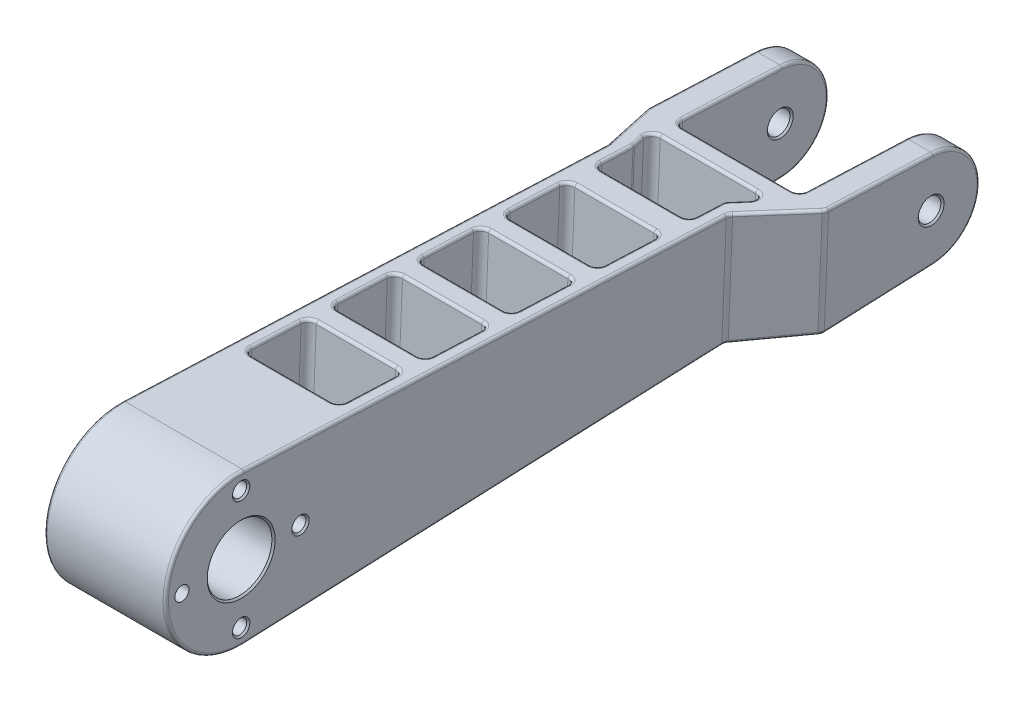
SolidWorks part; units mm, degrees
ref_plane "前视基准面" through (0, 0, 0) normal (0, 0, 1) x (1, 0, 0)
ref_plane "上视基准面" through (0, 0, 0) normal (0, 1, 0) x (1, 0, 0)
ref_plane "右视基准面" through (0, 0, 0) normal (1, 0, 0) x (0, 0, -1)
sketch "草图1" plane through (0, 0, 0) normal (1, 0, 0) x (0, 0, -1)
  line L0 (0.5833, 13.9878) -> (120.375, 8.9922)
  line L1 (0, -14.0122) -> (120.375, -8.9922)
  arc A0 (0.5833, 13.9878) -> (0.5833, -13.9878) centre (0, 0) ccw
  arc A1 (120.375, -8.9922) -> (120.375, 8.9922) centre (120, 0) ccw
  dimension "D1" = 28
  dimension "D2" = 18
  dimension "D3" = 120
extrude "凸台-拉伸1" add sketch "草图1" along normal blind 33 contours L1 A1 L0 A0
sketch "草图2" plane through (0, 0, 0) normal (-1, 0, 0) x (0, 0, 1)
  line L0 (11, 0) -> (0, 0) construction
  line L3 (-120.375, -8.9922) -> (-0.5833, -13.9878)
  line L4 (-0.5833, 13.9878) -> (-120.375, 8.9922)
  line L5 (-120.375, -8.9922) -> (-0.5833, -13.9878)
  line L6 (-0.5833, 13.9878) -> (-120.375, 8.9922)
  circle A0 centre (0, 0) radius 6
  circle A2 centre (11, 0) radius 1.3108
  circle A3 centre (0, -11) radius 1.3108
  circle A4 centre (-11, 0) radius 1.3108
  circle A5 centre (0, 11) radius 1.3108
  circle A9 centre (-120, 0) radius 2.1
  arc A12 (-0.5833, -13.9878) -> (-0.5833, 13.9878) centre (0, 0) ccw
  arc A13 (-120.375, 8.9922) -> (-120.375, -8.9922) centre (-120, 0) ccw
  arc A14 (-0.5833, -13.9878) -> (-0.5833, 13.9878) centre (0, 0) ccw
  arc A15 (-120.375, 8.9922) -> (-120.375, -8.9922) centre (-120, 0) ccw
  point P14 (0, 0)
  dimension "D1" = 12
  dimension "D3" = 2.6216
  dimension "D8" = 4.2
  dimension "D2" = 11
  dimension "D5" = 15.5563
  dimension "D6" = 11
  dimension "D7" = 0
  dimension "D4" = 4
extrude "切除-拉伸1" cut sketch "草图2" against normal through all flip side to cut
sketch "草图5" plane through (0, 13.9878, -0.5833) normal (0, 0.9991, -0.0417) x (1, 0, 0)
  line L1 (22.5, 36) -> (22.5, 48)
  line L2 (22.5, 36) -> (5, 36)
  line L6 (33, 0) -> (0, 0) construction
  line L7 (13.75, 1) -> (13.75, 66.1042) construction
  line L8 (0, 100) -> (33, 100)
  line L9 (22.5, 20) -> (5, 20)
  line L10 (22.5, 20) -> (22.5, 32)
  line L11 (22.5, 32) -> (5, 32)
  line L12 (5, 20) -> (5, 32)
  line L13 (22.5, 20) -> (5, 32) construction
  line L14 (22.5, 32) -> (5, 20) construction
  line L15 (5, 36) -> (5, 48)
  line L16 (22.5, 48) -> (5, 48)
  line L17 (22.5, 52) -> (22.5, 64)
  line L18 (22.5, 52) -> (5, 52)
  line L19 (5, 52) -> (5, 64)
  line L20 (22.5, 64) -> (5, 64)
  line L21 (22.5, 68) -> (22.5, 80)
  line L22 (22.5, 68) -> (5, 68)
  line L23 (5, 68) -> (5, 80)
  line L25 (2.5, 90) -> (0, 100)
  line L27 (5, 100) -> (5, 146.1766)
  line L28 (5, 146.1766) -> (28, 146.1766)
  line L29 (28, 100) -> (28, 146.1766)
  line L30 (25, 90) -> (33, 100)
  line L31 (25, -28.3622) -> (25, 90)
  line L32 (0, 0) -> (0, 119.8958) construction
  line L33 (2.5, -28.3622) -> (25, -28.3622)
  line L34 (33, 0) -> (33, 119.8958) construction
  line L35 (5, 146.1766) -> (0, 146.1766)
  line L36 (2.5, -28.3622) -> (2.5, 90)
  line L37 (0, 146.1766) -> (0, -28.3622)
  line L38 (0, -28.3622) -> (33, -28.3622)
  line L39 (33, -28.3622) -> (33, 146.1766)
  line L40 (33, 146.1766) -> (28, 146.1766)
  line L42 (5, 92.3693) -> (3.9673, 96.5)
  line L43 (3.9673, 96.5) -> (26.3581, 96.5)
  line L44 (26.3581, 96.5) -> (22.5, 91.6773)
  line L46 (5, 80) -> (22.5, 80)
  line L47 (15.25, 80) -> (5, 80) [skipped]
  line L49 (5, 92.3693) -> (5, 85)
  line L50 (5, 85) -> (22.5, 85)
  line L51 (22.5, 85) -> (22.5, 91.6773)
  point P2 (16.5, 0)
  point P3 (13.75, 26)
  dimension "D2" = 5
  dimension "D3" = 6
  dimension "D5" = 16
  dimension "D6" = 46.1766
  dimension "D7" = 5
  dimension "D8" = 20
  dimension "D9" = 2.5
  dimension "D10" = 2.5
  dimension "D11" = 100
  dimension "D12" = 5
  dimension "D13" = 2.5
  dimension "D14" = 8
  dimension "D15" = 46.1766
  dimension "D16" = 28.3622
  dimension "D17" = 3.5
  dimension "D18" = 3
  dimension "D19" = 3
  dimension "D20" = 5
  dimension "D4" = 4
extrude "切除-拉伸3" cut sketch "草图5" against normal through all
chamfer "倒角2" distance 0.3 angle 45 13 edges at (25, -11, -1.3108) (2.5, -11, -1.3108) (25, 11, -1.3108) (2.5, 11, -1.3108) (25, 0, -12.3108) (2.5, 0, -12.3108) (25, 0, -6) (2.5, 0, -6) (33, 0, -117.9) (28, 0, -122.1) (5, 0, -122.1) (0, 0, -117.9) (2.5, 0, 9.6892)
fillet "圆角4" radius 1.4 28 edges at (5, -0.0229, -20.0164) (5, -0.0218, -36.0304) (5, -0.0206, -52.0443) (5, -0.022, -32.0269) (5, -0.0209, -48.0409) (5, -0.0197, -64.0548) (22.5, -0.022, -32.0269) (22.5, -0.0209, -48.0409) (22.5, -0.0229, -20.0164) (22.5, -0.0218, -36.0304) (22.5, -0.0206, -52.0443) (22.5, -0.0197, -64.0548) (5, -0.0194, -68.0583) (22.5, -0.0194, -68.0583) (5, -0.0171, -100.0862) (28, -0.0171, -100.0862) (33, -0.0171, -100.0862) (25, -0.0178, -90.0775) (0, -0.0171, -100.0862) (2.5, -0.0178, -90.0775) (26.3581, -0.0174, -96.5832) (3.9673, -0.0174, -96.5832) (5, -0.0182, -85.0731) (22.5, -0.0182, -85.0731) (22.5, -0.0177, -91.7563) (5, -0.0177, -92.4489) (22.5, -0.0186, -80.0688) (5, -0.0186, -80.0688)
fillet "圆角5" radius 0.5 124 edges at (2.5, 0, 14) (0, 0, -129) (5, 0, -129) (28, 0, -129) (25, 0, 14) (33, 0, -129) (5.4101, -12.7157, -31.0871) (13.75, -12.6986, -31.4982) (22.0899, -12.7157, -31.0871) (22.5, -12.9495, -25.4826) (22.0899, -13.1832, -19.878) (13.75, -13.2003, -19.4669) (5.4101, -13.1832, -19.878) (5, -12.9495, -25.4826) (28, -9.3945, -110.7273) (27.5899, -9.8383, -100.087) (16.5, -9.8554, -99.6759) (5.4101, -9.8383, -100.087) (5, -9.3945, -110.7273) (0, -9.4202, -110.1119) (0.0105, -9.8553, -99.6772) (1.25, -10.0645, -94.6629) (2.4895, -10.2736, -89.6485) (2.5, -12.1343, -45.0302) (25, -12.1409, -44.8704) (25.0789, -10.2747, -89.622) (29, -10.0645, -94.6629) (32.9211, -9.8542, -99.7037) (33, -9.4135, -110.2716) (5.4101, -12.5142, -35.9198) (5, -12.2805, -41.5244) (5.4101, -12.0468, -47.1289) (13.75, -12.0296, -47.5401) (22.0899, -12.0468, -47.1289) (22.5, -12.2805, -41.5244) (22.0899, -12.5142, -35.9198) (13.75, -12.5314, -35.5087) (5.4101, -11.8452, -51.9616) (5, -11.6115, -57.5662) (5.4101, -11.3778, -63.1707) (13.75, -11.3606, -63.5819) (22.0899, -11.3778, -63.1707) (22.5, -11.6115, -57.5662) (22.0899, -11.8452, -51.9616) (13.75, -11.8624, -51.5505) (5.4101, -11.1762, -68.0034) (5, -10.9425, -73.608) (22.5, -10.9425, -73.608) (22.0899, -11.1762, -68.0034) (13.75, -11.1934, -67.5923) (22.0899, 12.6716, -32.1458) (13.75, 12.6545, -32.5555) (5.4101, 12.6716, -32.1458) (5, 12.9045, -26.5608) (5.4101, 13.1374, -20.9757) (13.75, 13.1545, -20.566) (22.0899, 13.1374, -20.9757) (22.5, 12.9045, -26.5608) (25.0789, 10.239, -90.4775) (25, 12.1231, -45.2989) (2.5, 12.1164, -45.4582) (2.4895, 10.2379, -90.5039) (1.25, 10.0295, -95.5008) (0.0105, 9.8211, -100.4978) (0, 9.4031, -110.5218) (5, 9.3775, -111.1351) (5.4101, 9.8041, -100.9062) (16.5, 9.8212, -100.4965) (27.5899, 9.8041, -100.9062) (28, 9.3775, -111.1351) (33, 9.3964, -110.6811) (32.9211, 9.82, -100.5241) (29, 10.0295, -95.5008) (22.0899, 12.0049, -48.132) (13.75, 11.9878, -48.5416) (5.4101, 12.0049, -48.132) (5, 12.2378, -42.5469) (5.4101, 12.4708, -36.9618) (13.75, 12.4878, -36.5521) (22.0899, 12.4708, -36.9618) (22.5, 12.2378, -42.5469) (22.0899, 11.3383, -64.1181) (13.75, 11.3212, -64.5278) (5.4101, 11.3383, -64.1181) (5, 11.5712, -58.533) (5.4101, 11.8041, -52.9479) (13.75, 11.8212, -52.5382) (22.0899, 11.8041, -52.9479) (22.5, 11.5712, -58.533) (5, 10.9045, -74.5191) (5.4101, 11.1374, -68.934) (13.75, 11.1545, -68.5243) (22.0899, 11.1374, -68.934) (22.5, 10.9045, -74.5191) (4.6802, -10.121, -93.3078) (4.6569, -10.0242, -95.6269) (14.6028, -10.0017, -96.1668) (24.7071, -10.0349, -95.3712) (23.6726, -10.1421, -92.8011) (24.7071, 10.0001, -96.2067) (14.6028, 9.967, -96.9995) (4.6569, 9.9894, -96.4616) (4.6802, 10.0858, -94.1505) (23.6726, 10.1069, -93.6456) (13.75, -10.6916, -79.6237) (22.0899, -10.4654, -85.0478) (13.75, -10.4826, -84.6367) (5.4101, -10.4654, -85.0478) (5, -10.3028, -88.9464) (4.9895, -10.1745, -92.024) (22.5789, -10.2045, -91.3038) (22.5, -10.324, -88.4398) (13.75, 10.6545, -80.5139) (4.9895, 10.1392, -92.8711) (5, 10.2671, -89.8043) (5.4101, 10.4291, -85.9192) (13.75, 10.4462, -85.5095) (22.0899, 10.4291, -85.9192) (22.5, 10.2881, -89.2993) (22.5789, 10.1691, -92.1534) (22.0899, -10.7088, -79.2125) (5.4101, -10.7088, -79.2125) (22.0899, 10.6716, -80.1042) (5.4101, 10.6716, -80.1042)
